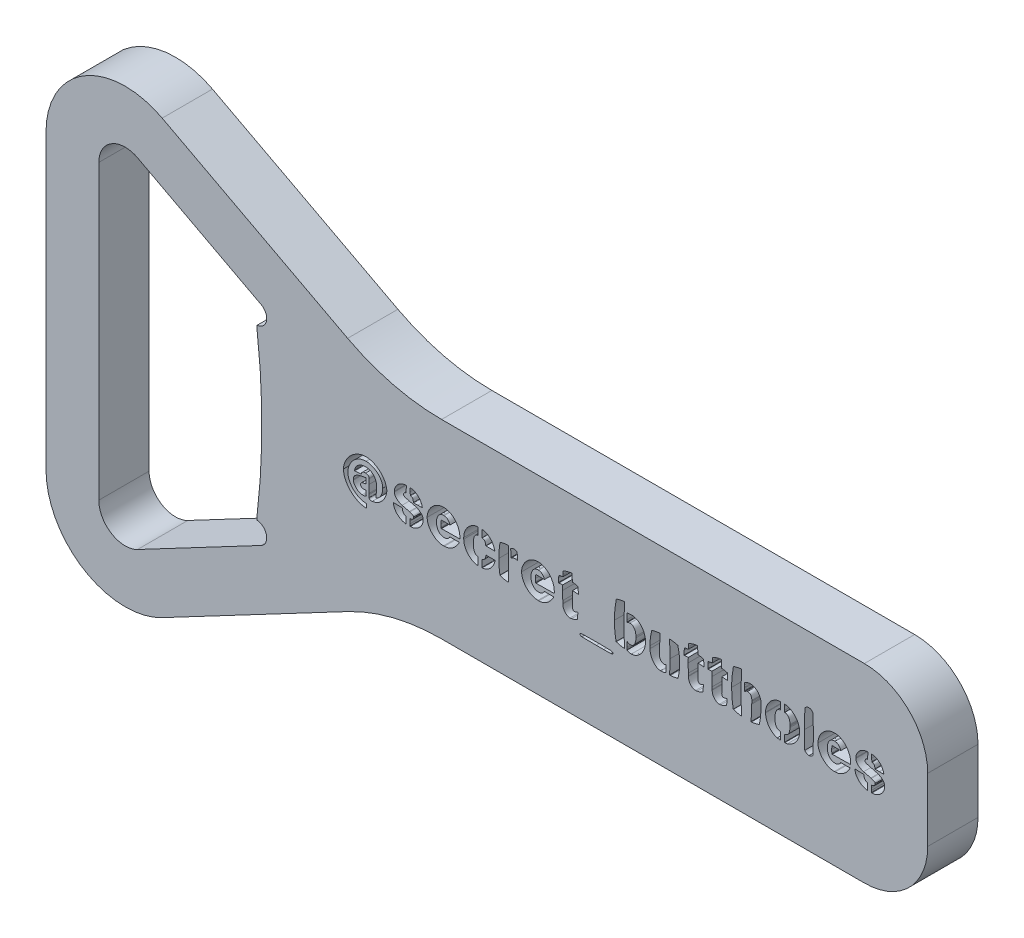
SolidWorks part; units mm, degrees
ref_plane "Front Plane" through (0, 0, 0) normal (0, 0, 1) x (1, 0, 0)
ref_plane "Top Plane" through (0, 0, 0) normal (0, 1, 0) x (1, 0, 0)
ref_plane "Right Plane" through (0, 0, 0) normal (1, 0, 0) x (0, 0, -1)
sketch "Model" plane through (0, 0, 0) normal (0, 0, 1) x (1, 0, 0)
  line L0 (93.451, 245.0307) -> (75.8892, 254.3082)
  line L1 (64.8859, 247.6767) -> (64.8859, 219.9729)
  line L2 (75.8892, 213.3414) -> (93.451, 222.6188)
  line L3 (102.3493, 224.8248) -> (142.3859, 224.8248)
  line L4 (73.5537, 217.7624) -> (85.2574, 223.9452)
  line L5 (69.8859, 247.6767) -> (69.8859, 219.9729)
  line L6 (85.2574, 243.7044) -> (73.5537, 249.8872)
  line L7 (84.8859, 225.8248) -> (84.8859, 226.3248)
  line L8 (84.8859, 241.3248) -> (84.8859, 241.8248)
  line L9 (142.3859, 242.8248) -> (102.3493, 242.8248)
  line L10 (148.3859, 230.8248) -> (148.3859, 236.8248)
  arc A0 (93.451, 245.0307) -> (102.3493, 242.8248) centre (102.3493, 261.8748) ccw
  arc A1 (75.8892, 254.3082) -> (64.8859, 247.6767) centre (72.3859, 247.6767) ccw
  arc A2 (64.8859, 219.9729) -> (75.8892, 213.3414) centre (72.3859, 219.9729) ccw
  arc A3 (102.3493, 224.8248) -> (93.451, 222.6188) centre (102.3493, 205.7748) ccw
  arc A4 (69.8859, 219.9729) -> (73.5537, 217.7624) centre (72.3859, 219.9729) ccw
  arc A5 (73.5537, 249.8872) -> (69.8859, 247.6767) centre (72.3859, 247.6767) ccw
  arc A6 (85.2574, 223.9452) -> (85.7424, 225.1352) centre (84.7903, 224.8294) ccw
  arc A7 (85.7424, 242.5144) -> (85.2574, 243.7044) centre (84.7903, 242.8202) ccw
  arc A9 (85.7424, 225.1352) -> (84.8859, 225.8248) centre (84.7903, 224.8294) ccw
  arc A10 (84.8859, 226.3248) -> (84.8859, 241.3248) centre (21.8304, 233.8248) ccw
  arc A11 (84.8859, 241.8248) -> (85.7424, 242.5144) centre (84.7903, 242.8202) ccw
  arc A12 (148.3859, 236.8248) -> (142.3859, 242.8248) centre (142.3859, 236.8248) ccw
  arc A13 (142.3859, 224.8248) -> (148.3859, 230.8248) centre (142.3859, 230.8248) ccw
extrude "Boss-Extrude1" add sketch "Model" along normal blind 4.7625
sketch "Sketch2" plane through (0, 0, 4.7625) normal (0, 0, 1) x (1, 0, 0)
  line L8 (136.9559, 226.9668) -> (136.9559, 230.7587)
  line L9 (139.4959, 226.9668) -> (139.4959, 230.7587)
  line L11 (132.4785, 229.8735) -> (135.1599, 232.5548)
  line L12 (134.2746, 228.0774) -> (136.9559, 230.7587)
  line L14 (131.3679, 235.0948) -> (135.1599, 235.0948)
  line L15 (131.3679, 232.5548) -> (135.1599, 232.5548)
  line L17 (134.2746, 239.5721) -> (136.9559, 236.8908)
  line L18 (132.4785, 237.7761) -> (135.1599, 235.0948)
  line L19 (136.9559, 236.8908) -> (136.9559, 240.6828)
  line L21 (139.4959, 236.8908) -> (142.1772, 239.5721)
  line L22 (139.4959, 236.8908) -> (139.4959, 240.6828)
  line L23 (141.292, 235.0948) -> (145.0839, 235.0948)
  line L24 (141.292, 235.0948) -> (143.9733, 237.7761)
  line L25 (141.292, 232.5548) -> (143.9733, 229.8735)
  line L26 (141.292, 232.5548) -> (145.0839, 232.5548)
  line L28 (139.4959, 230.7587) -> (142.1772, 228.0774)
  arc A0 (136.9559, 226.9668) -> (139.4959, 226.9668) centre (138.2259, 226.9668) ccw
  arc A1 (139.4959, 240.6828) -> (136.9559, 240.6828) centre (138.2259, 240.6828) ccw
  arc A2 (132.4785, 229.8735) -> (134.2746, 228.0774) centre (133.3766, 228.9754) ccw
  arc A3 (143.9733, 237.7761) -> (142.1772, 239.5721) centre (143.0752, 238.6741) ccw
  arc A4 (131.3679, 235.0948) -> (131.3679, 232.5548) centre (131.3679, 233.8248) ccw
  arc A5 (145.0839, 232.5548) -> (145.0839, 235.0948) centre (145.0839, 233.8248) ccw
  arc A6 (134.2746, 239.5721) -> (132.4785, 237.7761) centre (133.3766, 238.6741) ccw
  arc A7 (142.1772, 228.0774) -> (143.9733, 229.8735) centre (143.0752, 228.9754) ccw
  dimension "D4" = 2.54
  dimension "D5" = 2.54
  dimension "D6" = 2.54
  dimension "D7" = 2.54
extrude "Cut-Extrude1" [suppressed] cut sketch "Sketch2" against normal through all
fillet "Fillet1" [suppressed] radius 0.127
sketch "Sketch3" plane through (0, 0, 4.7625) normal (0, 0, 1) x (1, 0, 0)
  line L0 (144.5037, 232.5943) -> (85.3304, 232.5943) construction
  text T0 "@secret_buttholes" font "Stencilia-Bold" height in points 12
  point P2 (144.5037, 233.8248)
  point P3 (0, 0)
  point P4 (85.3304, 233.8248)
  point P9 (148.3859, 233.8248)
extrude "Cut-Extrude2" cut sketch "Sketch3" against normal through all
